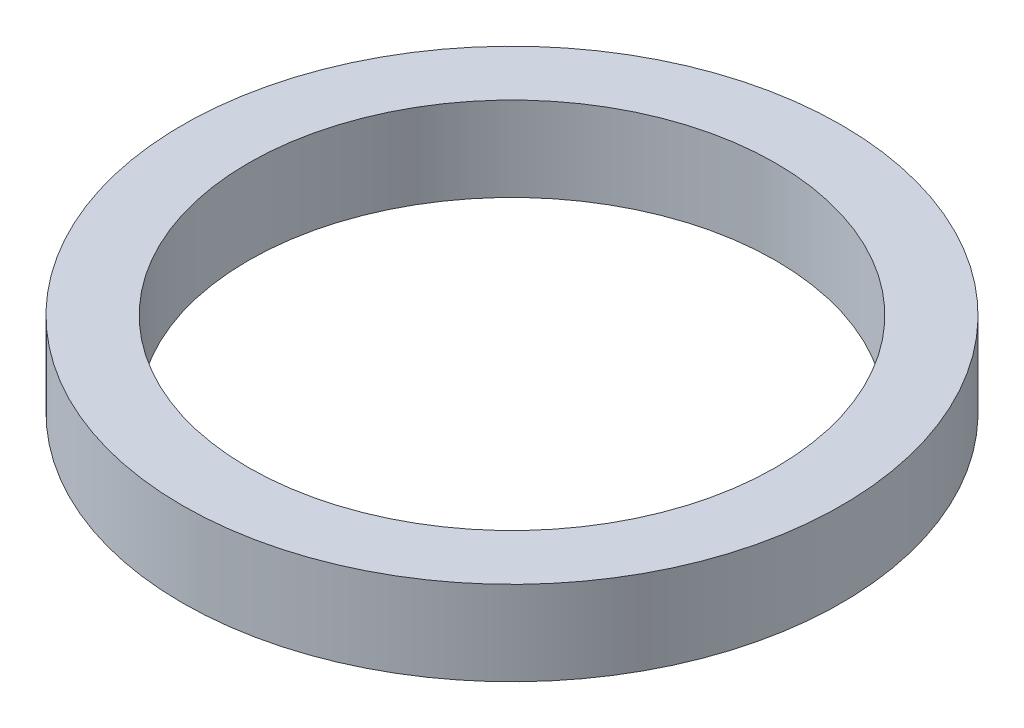
SolidWorks part; units mm, degrees
ref_plane "Front Plane" through (0, 0, 0) normal (0, 0, 1) x (1, 0, 0)
ref_plane "Top Plane" through (0, 0, 0) normal (0, 1, 0) x (1, 0, 0)
ref_plane "Right Plane" through (0, 0, 0) normal (1, 0, 0) x (0, 0, -1)
sketch "Sketch1" plane through (0, 0, 0) normal (0, 1, 0) x (1, 0, 0)
  circle A0 centre (0, 0) radius 62.5
  dimension "FLANGE_OD" = 125
extrude "Boss-Extrude1" add sketch "Sketch1" along normal blind 16
sketch "Sketch2" plane through (0, 0, 0) normal (0, 1, 0) x (1, 0, 0)
  circle A0 centre (0, 0) radius 50
  dimension "BORE_D" = 100
extrude "Cut-Extrude1" cut sketch "Sketch2" along normal through all
sketch "Sketch3" plane through (0, 16, 0) normal (0, 1, 0) x (1, 0, 0)
  circle A0 centre (0, 0) radius 29.3234 construction
  circle A1 centre (-29.3234, 0) radius 1.7422
  dimension "BOLT_D" = 3.4844
  dimension "BOLT_PCD" = 58.6467
extrude "Cut-Extrude2" cut sketch "Sketch3" against normal blind 14.4175 rebuild error yes
pattern_circular "CirPattern1" count 3 over 360 rebuild error yes
